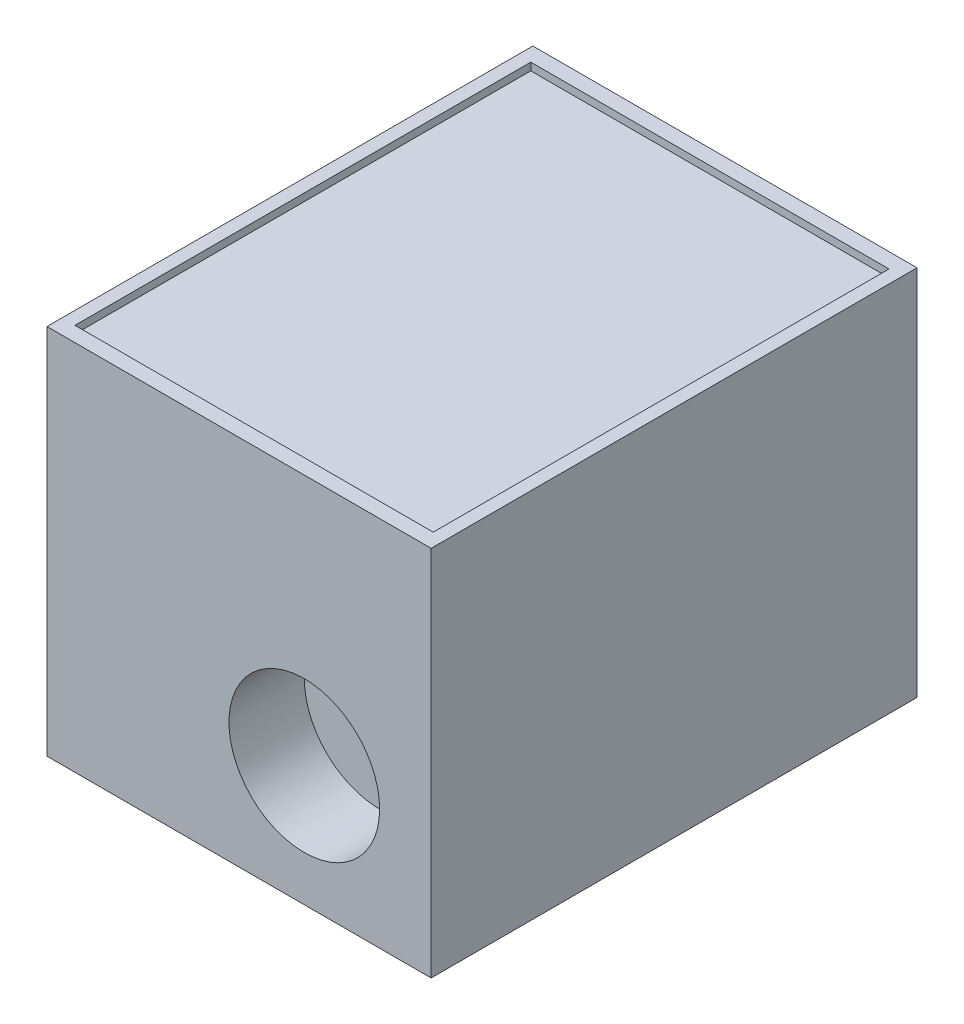
SolidWorks part; units mm, degrees
ref_plane "Front Plane" through (0, 0, 0) normal (0, 0, 1) x (1, 0, 0)
ref_plane "Top Plane" through (0, 0, 0) normal (0, 1, 0) x (1, 0, 0)
ref_plane "Right Plane" through (0, 0, 0) normal (1, 0, 0) x (0, 0, -1)
sketch "Sketch1" plane through (0, 0, 0) normal (0, 1, 0) x (1, 0, 0)
  line L1 (25.5, -32.25) -> (-25.5, -32.25)
  line L2 (25.5, -32.25) -> (25.5, 32.25)
  line L3 (25.5, 32.25) -> (-25.5, 32.25)
  line L4 (-25.5, -32.25) -> (-25.5, 32.25)
  line L5 (25.5, -32.25) -> (-25.5, 32.25) construction
  line L6 (25.5, 32.25) -> (-25.5, -32.25) construction
  point P0 (0, 0)
  dimension "D1" = 51
  dimension "D2" = 64.5
extrude "Boss-Extrude1" add sketch "Sketch1" along normal blind 49.4
sketch "Sketch2" plane through (0, 0, 32.25) normal (0, 0, 1) x (1, 0, 0)
  line L0 (25.5, 49.4) -> (25.5, 0) construction
  line L1 (-25.5, 0) -> (25.5, 0) construction
  circle A0 centre (8.66, 16) radius 10
  dimension "D1" = 16.84
  dimension "D2" = 16
  dimension "D3" = 20
extrude "Cut-Extrude1" cut sketch "Sketch2" against normal blind 10
ref_axis "Axis1" through (8.66, 16, 22.25) along (0, 0, 1)
sketch "Sketch3" plane through (0, 49.4, 0) normal (0, 1, 0) x (1, 0, 0)
  line L1 (23.7782, -30.2548) -> (-23.7782, -30.2548)
  line L2 (23.7782, -30.2548) -> (23.7782, 30.2548)
  line L3 (23.7782, 30.2548) -> (-23.7782, 30.2548)
  line L4 (-23.7782, -30.2548) -> (-23.7782, 30.2548)
  line L5 (23.7782, -30.2548) -> (-23.7782, 30.2548) construction
  line L6 (23.7782, 30.2548) -> (-23.7782, -30.2548) construction
  point P0 (0, 0)
extrude "Cut-Extrude2" cut sketch "Sketch3" against normal blind 1
sketch "Sketch4" plane through (0, 0, 0) normal (0, -1, 0) x (1, 0, 0)
  line L0 (25.5, 32.25) -> (25.5, -32.25) construction
  line L1 (-5.5, -13.25) -> (14.5, -13.25) construction
  line L2 (-5.5, -13.25) -> (-5.5, 27.25) construction
  line L3 (-5.5, 27.25) -> (14.5, 27.25) construction
  line L4 (14.5, -13.25) -> (14.5, 27.25) construction
  line L5 (-5.5, -13.25) -> (14.5, 27.25) construction
  line L6 (-5.5, 27.25) -> (14.5, -13.25) construction
  line L8 (-25.5, 32.25) -> (25.5, 32.25) construction
  circle A0 centre (-5.5, 27.25) radius 1.75
  circle A1 centre (14.5, 27.25) radius 1.75
  circle A2 centre (14.5, -13.25) radius 1.75
  circle A3 centre (-5.5, -13.25) radius 1.75
  point P0 (4.5, 7)
  dimension "D4" = 3.5
  dimension "D1" = 31
  dimension "D2" = 5
  dimension "D3" = 11
  dimension "D5" = 45.5
extrude "Cut-Extrude3" cut sketch "Sketch4" against normal blind 5
